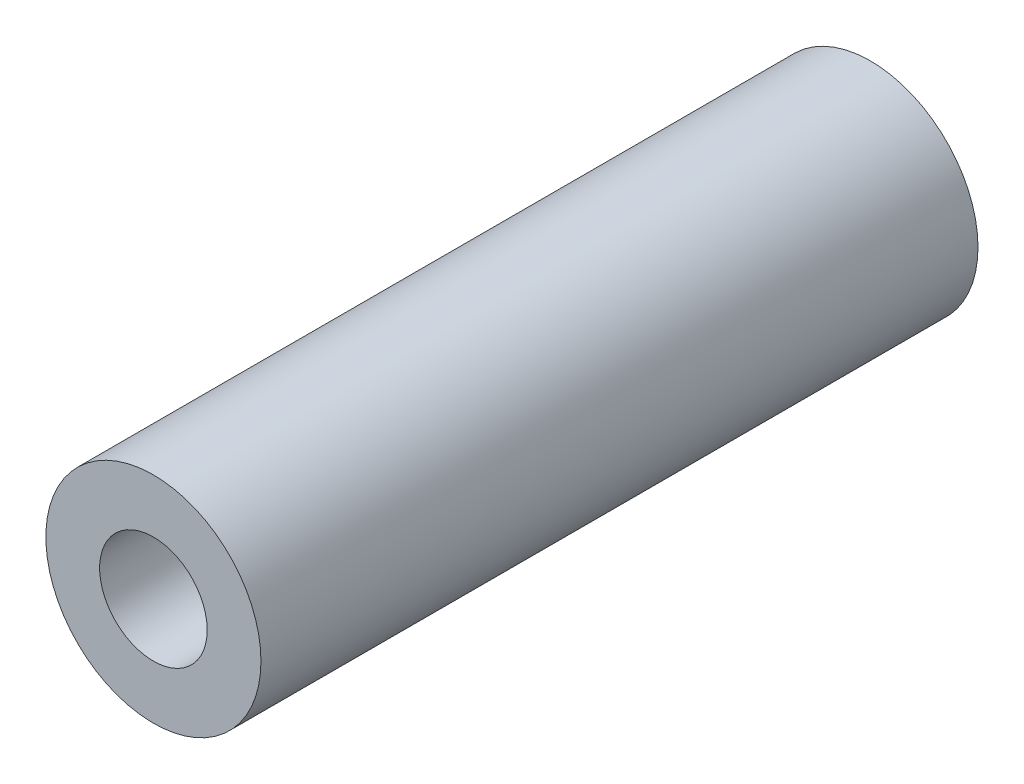
SolidWorks part; units mm, degrees
ref_plane "正面" through (0, 0, 0) normal (0, 0, 1) x (1, 0, 0)
ref_plane "平面" through (0, 0, 0) normal (0, 1, 0) x (1, 0, 0)
ref_plane "右側面" through (0, 0, 0) normal (1, 0, 0) x (0, 0, -1)
sketch "ｽｹｯﾁ1" plane through (0, 0, 0) normal (0, 0, 1) x (1, 0, 0)
  circle A0 centre (0, 0) radius 3
  circle A1 centre (0, 0) radius 1.5
  dimension "D1" = 6
  dimension "D2" = 3
extrude "ﾎﾞｽ - 押し出し1" add sketch "ｽｹｯﾁ1" along normal blind 20
